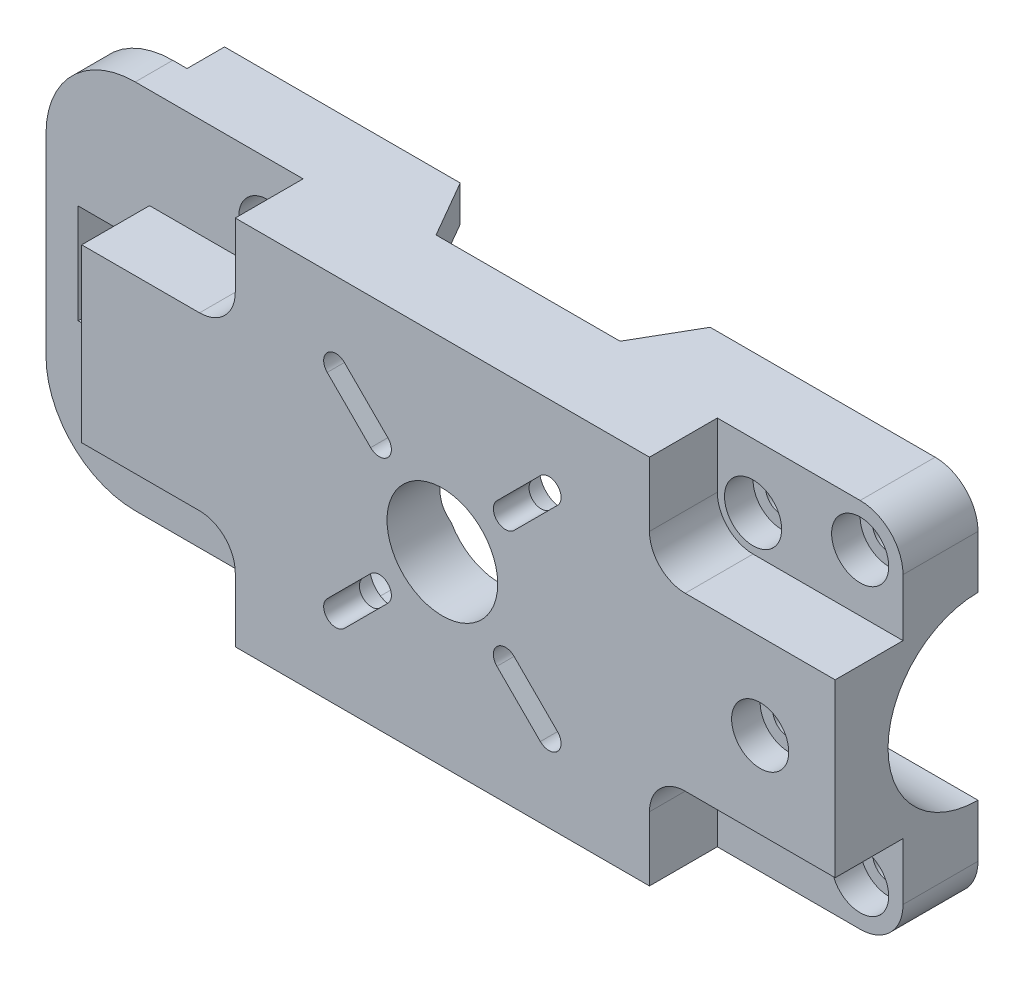
SolidWorks part; units mm, degrees
material "ABS"
ref_plane "Front Plane" through (0, 0, 0) normal (0, 0, 1) x (1, 0, 0)
ref_plane "Top Plane" through (0, 0, 0) normal (0, 1, 0) x (1, 0, 0)
ref_plane "Right Plane" through (0, 0, 0) normal (1, 0, 0) x (0, 0, -1)
sketch "Sketch2" plane through (0, 0, 0) normal (0, 0, 1) x (1, 0, 0)
  line L1 (54, 26) -> (-47.5, 26)
  line L2 (60, 20) -> (60, -20)
  line L3 (54, -26) -> (-47.5, -26)
  line L4 (-60, 13.5) -> (-60, -13.5)
  line L5 (60, 26) -> (-60, -26) construction
  line L6 (60, -26) -> (-60, 26) construction
  arc A0 (60, -20) -> (54, -26) centre (54, -20) cw
  arc A1 (54, 26) -> (60, 20) centre (54, 20) cw
  arc A2 (-47.5, -26) -> (-60, -13.5) centre (-47.5, -13.5) cw
  arc A3 (-47.5, 26) -> (-60, 13.5) centre (-47.5, 13.5) ccw
  point P0 (0, 0)
  dimension "D3" = 6
  dimension "D4" = 12.5
  dimension "D1" = 52
  dimension "D2" = 120
extrude "Boss-Extrude2" add sketch "Sketch2" along normal blind 20
sketch "Sketch3" plane through (0, 0, 20) normal (0, 0, 1) x (1, 0, 0)
  line L0 (60, -12) -> (39, -12)
  line L1 (34, -17) -> (34, -26)
  line L2 (34, 17) -> (34, 26)
  line L3 (39, 12) -> (60, 12)
  line L4 (60, -20) -> (60, 20)
  line L5 (54, 26) -> (-47.5, 26)
  line L6 (-60, 13.5) -> (-60, -13.5)
  line L7 (-47.5, -26) -> (54, -26)
  line L8 (60, -20) -> (60, 20)
  line L9 (54, 26) -> (34, 26)
  line L10 (-60, 13.5) -> (-60, -13.5)
  line L11 (-47.5, -26) -> (-24, -26)
  line L12 (-24, 26) -> (-24, 17)
  line L13 (-29, 12) -> (-45.5, 12)
  line L14 (-45.5, -12) -> (-29, -12)
  line L15 (-24, -17) -> (-24, -26)
  line L16 (-45.5, -12) -> (-45.5, 12)
  line L17 (34, -26) -> (54, -26)
  line L18 (-24, 26) -> (-47.5, 26)
  arc A0 (39, -12) -> (34, -17) centre (39, -17) ccw
  arc A1 (34, 17) -> (39, 12) centre (39, 17) ccw
  arc A2 (-24, 17) -> (-29, 12) centre (-29, 17) cw
  arc A3 (-29, -12) -> (-24, -17) centre (-29, -17) cw
  arc A4 (54, -26) -> (60, -20) centre (54, -20) ccw
  arc A5 (60, 20) -> (54, 26) centre (54, 20) ccw
  arc A6 (-47.5, 26) -> (-60, 13.5) centre (-47.5, 13.5) ccw
  arc A7 (-60, -13.5) -> (-47.5, -26) centre (-47.5, -13.5) ccw
  arc A8 (54, -26) -> (60, -20) centre (54, -20) ccw
  arc A9 (60, 20) -> (54, 26) centre (54, 20) ccw
  arc A10 (-47.5, 26) -> (-60, 13.5) centre (-47.5, 13.5) ccw
  arc A11 (-60, -13.5) -> (-47.5, -26) centre (-47.5, -13.5) ccw
  point P20 (34, -12)
  point P30 (-24, 12)
  point P35 (-24, -12)
  arc M12 (54, -26) -> (60, -20) centre (54, -20) ccw
  line M13 (60, -20) -> (60, 20)
  arc M14 (60, 20) -> (54, 26) centre (54, 20) ccw
  line M15 (54, 26) -> (-47.5, 26)
  arc M16 (-47.5, 26) -> (-60, 13.5) centre (-47.5, 13.5) ccw
  line M17 (-60, 13.5) -> (-60, -13.5)
  arc M18 (-60, -13.5) -> (-47.5, -26) centre (-47.5, -13.5) ccw
  line M19 (-47.5, -26) -> (54, -26)
  dimension "D4" = 5
  dimension "D7" = 5
  dimension "D2" = 26
  dimension "D3" = 14
  dimension "D5" = 14.5
  dimension "D6" = 36
  dimension "D1" = 0
extrude "Cut-Extrude1" cut sketch "Sketch3" against normal blind 9.5 contours A3 L14 L16 L13 A2 L12 L15 M15 M16 M17 M18 M19 | L2 A1 L3 M13 M14 M15 | L0 A0 L1 M19 M12 M13 region at (46.925, -18.9653, 20) region at (46.925, 18.9653, 20) region at (-35.75, -25.3675, 20)
hole_wizard "CBORE for M4 SHCS1" positions "Sketch4" profile "Sketch5" counterbore size "M4" standard "ANSI Metric" end condition through all
sketch "Sketch4" plane through (0, 0, 10.5) normal (0, 0, 1) x (1, 0, 0)
  point P0 (39, -17)
  point P3 (39, 17)
  point P6 (-29, 17)
  point P13 (-29, -17)
  point P16 (54, 20)
  point P21 (54, -20)
sketch "Sketch5" plane through (39, -17, 10.5) normal (1, 0, 0) x (0, -1, 0)
  line L0 (0, 0) -> (0, 10.5)
  line L1 (0, 10.5) -> (2.25, 10.5)
  line L3 (2.25, 10.5) -> (2.25, 4)
  line L4 (2.25, 4) -> (4, 4)
  line L5 (4, 4) -> (4, 0)
  line L7 (4, 0) -> (0, 0)
  line L11 (0, -6.35) -> (0, 107.95) construction
  dimension "Thru Hole Dia." = 4.5
  dimension "Thru Hole Depth" = 10.5
  dimension "C'Bore Dia." = 8
  dimension "C'Bore Depth" = 4
sketch "Sketch6" plane through (0, 0, 0) normal (0, 0, 1) x (1, 0, 0)
  line L0 (39, -17) -> (-29, 17) construction
  line L1 (25, -21) -> (-15, -21)
  line L2 (30, -16) -> (30, 16)
  line L3 (25, 21) -> (-15, 21)
  line L4 (-20, -16) -> (-20, 16)
  line L5 (30, -21) -> (-20, 21) construction
  line L6 (30, 21) -> (-20, -21) construction
  arc A0 (-15, -21) -> (-20, -16) centre (-15, -16) cw
  arc A1 (30, 16) -> (25, 21) centre (25, 16) ccw
  arc A2 (25, -21) -> (30, -16) centre (25, -16) ccw
  arc A3 (-15, 21) -> (-20, 16) centre (-15, 16) ccw
  point P0 (5, 0)
  point P9 (5, 0)
  dimension "D1" = 5
  dimension "D2" = 42
  dimension "D3" = 50
extrude "Cut-Extrude2" cut sketch "Sketch6" along normal blind 12
sketch "Sketch7" plane through (0, 0, 0) normal (0, 1, 0) x (1, 0, 0)
  line L0 (-12.5, 0) -> (22.5, 0)
  line L1 (-47.5, 0) -> (54, 0) construction
  line L2 (22.5, 0) -> (17.8812, -8)
  line L3 (17.8812, -8) -> (-7.8812, -8)
  line L4 (-7.8812, -8) -> (-12.5, 0)
  line L5 (5, 0) -> (5, -20) construction
  line L6 (-24, -20) -> (34, -20) construction
  point P6 (5, 0)
  dimension "D1" = 60
  dimension "D2" = 35
  dimension "D3" = 8
extrude "Cut-Extrude3" cut sketch "Sketch7" against normal through all both and the other way through all
hole_wizard "CBORE SLOT for M3 SHCS1" positions "Sketch8" profile "Sketch9" size "M3" standard "ANSI Metric" slot yes end condition up to next
sketch "Sketch8" plane through (0, 0, 12) normal (0, 0, -1) x (-1, 0, 0)
  line L0 (-21.122, -16.122) -> (-12.6368, -7.6368) construction
  line L1 (-16.8794, -11.8794) -> (6.8794, 11.8794) construction
  line L3 (29, -17) -> (-39, 17) construction
  line L4 (6.8794, 11.8794) -> (6.8794, -11.8794) construction
  line L5 (6.8794, -11.8794) -> (-16.8794, -11.8794) construction
  point P0 (-16.8794, -11.8794)
  point P4 (6.8794, 11.8794)
  point P16 (-5, 0)
  dimension "D1" = 12
  dimension "D2" = 10.8
sketch "Sketch9" plane through (16.8794, -11.8794, 12) normal (1, 0, 0) x (0, 1, 0)
  line L0 (0, 0) -> (0, 8.001)
  line L1 (0, 8.001) -> (1.7, 8.001)
  line L3 (1.7, 8.001) -> (1.7, 3)
  line L4 (1.7, 3) -> (3.25, 3)
  line L5 (3.25, 3) -> (3.25, 0)
  line L7 (3.25, 0) -> (0, 0)
  line L11 (0, -6.35) -> (0, 107.95) construction
  dimension "Thru Hole Dia." = 3.4
  dimension "Thru Hole Depth" = 8.001
  dimension "C'Bore Dia." = 6.5
  dimension "C'Bore Depth" = 3
mirror "Mirror1" about plane through (0, 0, 0) normal (0, 1, 0) of "CBORE SLOT for M3 SHCS1"
sketch "Sketch10" plane through (-45.5, 0, 0) normal (-1, 0, 0) x (0, 0, 1)
  line L0 (0, 13.5) -> (0, -13.5) construction
  line L1 (0, 12.6) -> (0, -12.6)
  arc A0 (0, 12.6) -> (0, -12.6) centre (0, 0) cw
  dimension "D1" = 12.6
extrude "Cut-Extrude4" cut sketch "Sketch10" against normal through all and the other way blind 10
hole_wizard "M14 Clearance Hole1" positions "Sketch11" profile "Sketch12" hole size "M14" standard "ANSI Metric" end condition through all
sketch "Sketch11" plane through (0, 0, 20) normal (0, 0, 1) x (1, 0, 0)
  line L0 (13.8388, 8.8388) -> (-3.8388, -8.8388) construction
  point P0 (5, 0)
sketch "Sketch12" plane through (5, 0, 20) normal (1, 0, 0) x (0, -1, 0)
  line L0 (0, 0) -> (0, 20)
  line L1 (0, 20) -> (7.75, 20)
  line L2 (7.75, 20) -> (7.75, 0)
  line L5 (7.75, 0) -> (0, 0)
  line L11 (0, -6.35) -> (0, 107.95) construction
  dimension "Thru Hole Dia." = 15.5
  dimension "Thru Hole Depth" = 20
hole_wizard "CBORE for M4 SHCS2" positions "Sketch14" profile "Sketch15" counterbore size "M4" standard "ANSI Metric" end condition through all
sketch "Sketch14" plane through (0, 0, 20) normal (0, 0, 1) x (1, 0, 0)
  line L0 (-45.5, -12) -> (-45.5, 12) construction
  line L1 (49.5, 0) -> (0, 0) construction
  point P0 (49.5, 0)
  dimension "D1" = 95
sketch "Sketch15" plane through (49.5, 0, 20) normal (1, 0, 0) x (0, -1, 0)
  line L0 (0, 0) -> (0, 20)
  line L1 (0, 20) -> (2.25, 20)
  line L3 (2.25, 20) -> (2.25, 4)
  line L4 (2.25, 4) -> (4, 4)
  line L5 (4, 4) -> (4, 0)
  line L7 (4, 0) -> (0, 0)
  line L11 (0, -6.35) -> (0, 107.95) construction
  dimension "Thru Hole Dia." = 4.5
  dimension "Thru Hole Depth" = 20
  dimension "C'Bore Dia." = 8
  dimension "C'Bore Depth" = 4
sketch "Sketch16" plane through (0, 0, 0) normal (0, 0, -1) x (-1, 0, 0)
  line L0 (55.5, 12.6) -> (20, 12.6) construction
  line L1 (55.5, 6.9649) -> (38.5, 6.9649)
  line L2 (55.5, 6.9649) -> (55.5, 12.6)
  line L3 (55.5, 12.6) -> (38.5, 12.6)
  line L4 (38.5, 6.9649) -> (38.5, 12.6)
  line L5 (55.5, -12.6) -> (20, -12.6) construction
  line L6 (55.5, -6.9649) -> (38.5, -6.9649)
  line L7 (55.5, -6.9649) -> (55.5, -12.6)
  line L8 (55.5, -12.6) -> (38.5, -12.6)
  line L9 (38.5, -6.9649) -> (38.5, -12.6)
  line L10 (38.5, 6.9649) -> (38.5, -6.9649) construction
  line L12 (45.5, -6.9649) -> (45.5, 6.9649) construction
  dimension "D1" = 7
extrude "Boss-Extrude3" add sketch "Sketch16" against normal up to next
sketch "Sketch18" plane through (0, 0, 0) normal (0, 1, 0) x (1, 0, 0)
  line L0 (-60, -10.5) -> (-60, 0) construction
  line L1 (-60, -5.25) -> (-45.5, -5.25)
  line L2 (-60, -5.25) -> (-60, 0)
  line L3 (-60, 0) -> (-45.5, 0)
  line L4 (-45.5, -5.25) -> (-45.5, 0)
  line L5 (-12.5, 0) -> (-47.5, 0) construction
  line L6 (-45.5, -10.5) -> (-45.5, -5.25) construction
extrude "Cut-Extrude5" cut sketch "Sketch18" against normal through all both and the other way through all
